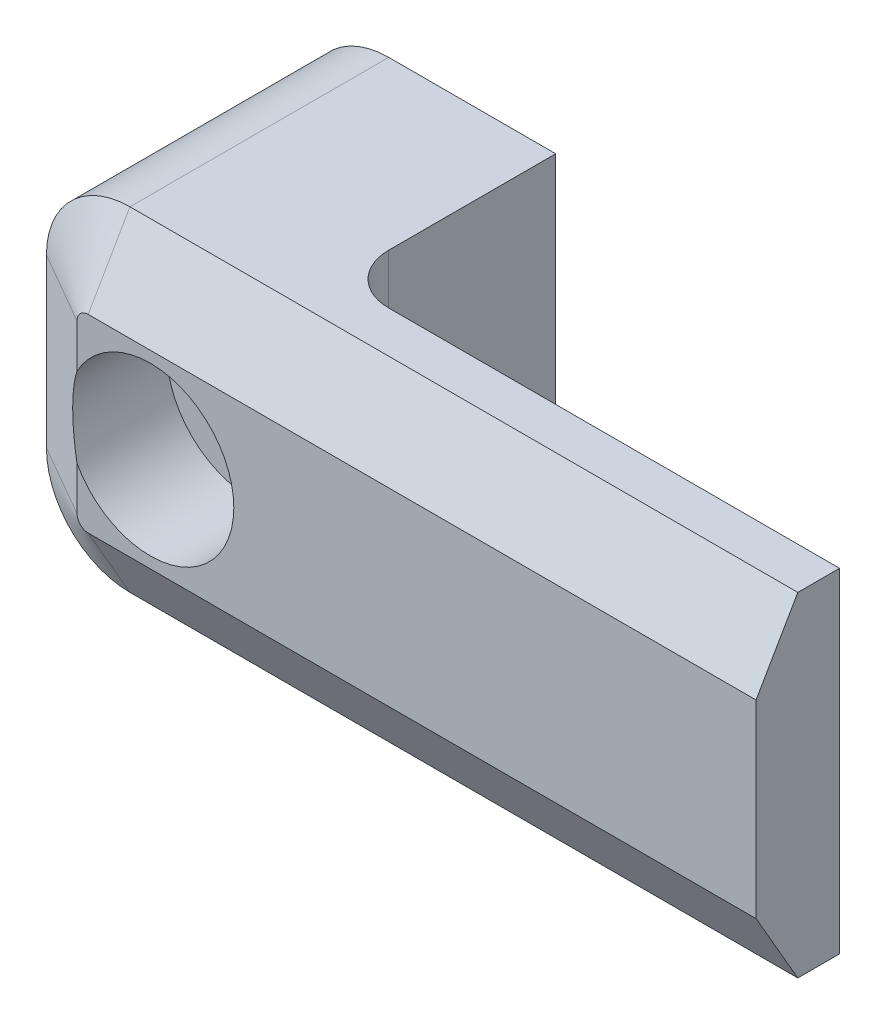
SolidWorks part; units mm, degrees
ref_plane "Front Plane" through (0, 0, 0) normal (0, 0, 1) x (1, 0, 0)
ref_plane "Top Plane" through (0, 0, 0) normal (0, 1, 0) x (1, 0, 0)
ref_plane "Right Plane" through (0, 0, 0) normal (1, 0, 0) x (0, 0, -1)
sketch "Sketch1" plane through (0, 0, 0) normal (0, 0, 1) x (1, 0, 0)
  line L1 (22.5, -10) -> (-22.5, -10)
  line L2 (22.5, -10) -> (22.5, 10)
  line L3 (22.5, 10) -> (-22.5, 10)
  line L4 (-22.5, -10) -> (-22.5, 10)
  line L5 (22.5, -10) -> (-22.5, 10) construction
  line L6 (22.5, 10) -> (-22.5, -10) construction
  point P0 (0, 0)
  dimension "D1" = 45
  dimension "D2" = 20
extrude "Extrude1" add sketch "Sketch1" along normal blind 5
sketch "Sketch2" plane through (0, 0, 0) normal (0, 0, -1) x (-1, 0, 0)
  line L0 (22.5, -10) -> (-22.5, -10) construction
  line L1 (22.5, 10) -> (7.5, 10)
  line L2 (22.5, 10) -> (22.5, -10)
  line L3 (22.5, -10) -> (7.5, -10)
  line L4 (7.5, 10) -> (7.5, -10)
  dimension "D1" = 15
extrude "Extrude2" add sketch "Sketch2" along normal blind 13
sketch "Sketch3" plane through (0, 0, 5) normal (0, 0, 1) x (1, 0, 0)
  line L0 (0, 0) -> (-24.4612, 0) construction
  circle A0 centre (-13.7784, 0) radius 5
  point P3 (-13.7784, 0)
extrude "Extrude3" cut sketch "Sketch3" against normal blind 6
sketch "Sketch4" plane through (0, 0, -1) normal (0, 0, 1) x (1, 0, 0)
  circle A0 centre (-13.7784, 0) radius 2.5
  dimension "D1" = 5
extrude "Extrude4" cut sketch "Sketch4" against normal blind 16
fillet "Fillet1" radius 5 2 edges at (-22.5, -10, -4) (-22.5, 10, -4)
chamfer "Chamfer1" distance 2.5 angle 60 5 edges at (2.5, -10, 5) (-21.0355, -8.5355, 5) (-22.5, 0, 5) (-21.0355, 8.5355, 5) (2.5, 10, 5) first distance on face at (-3.3333, -10, -3.75) first distance on face at (-20.5178, -8.0178, -4) first distance on face at (-22.5, 0, -4) first distance on face at (-20.5178, 8.0178, -4) first distance on face at (1.6667, 10, -3.75)
ref_plane "Plane1" through (-7.5, 10, 0) normal (0, -1, 0) x (-1, 0, 0)
fillet "Fillet2" radius 3 1 edges type face fillet first side face at (-7.5, 2.5, -9.75) second side face at (7.5, 2.5, 0)
